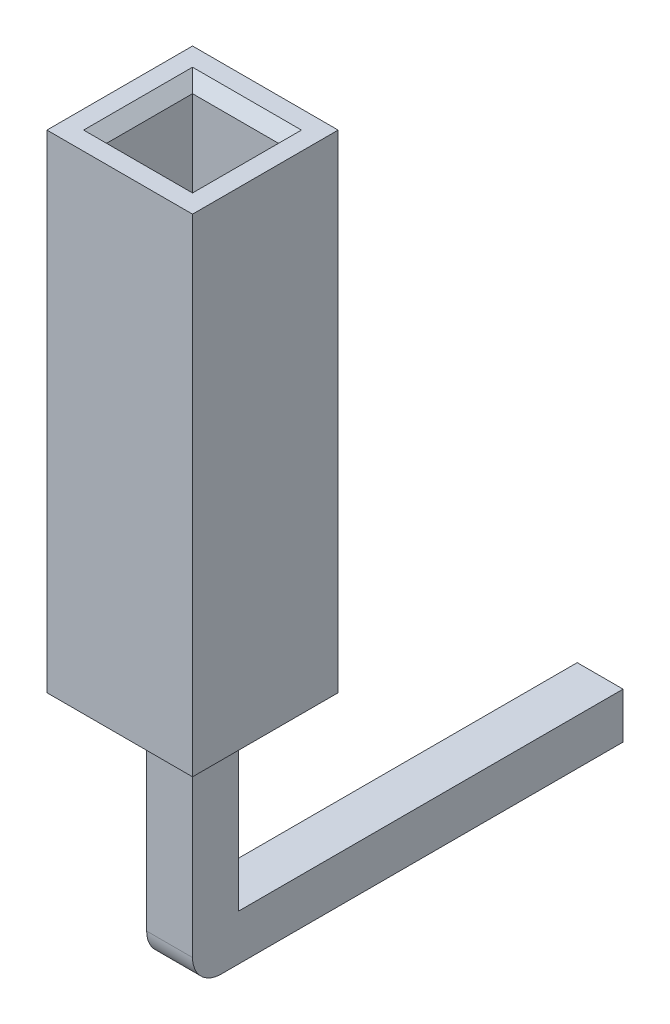
SolidWorks part; units mm, degrees
ref_plane "Спереди" through (0, 0, 0) normal (0, 0, 1) x (1, 0, 0)
ref_plane "Сверху" through (0, 0, 0) normal (0, 1, 0) x (1, 0, 0)
ref_plane "Справа" through (0, 0, 0) normal (1, 0, 0) x (0, 0, -1)
sketch "Эскиз1" plane through (0, 0, 0) normal (0, 1, 0) x (1, 0, 0)
  line L0 (1.27, 2.54) -> (1.27, 0) construction
  line L1 (0, 0) -> (2.54, 0)
  line L2 (0, 0) -> (0, 2.54)
  line L3 (0, 2.54) -> (2.54, 2.54)
  line L4 (2.54, 0) -> (2.54, 2.54)
  line L6 (0.52, 2.02) -> (2.02, 2.02)
  line L7 (0.52, 2.02) -> (0.52, 0.52)
  line L8 (0.52, 0.52) -> (2.02, 0.52)
  line L9 (2.02, 2.02) -> (2.02, 0.52)
  line L10 (0.52, 2.02) -> (2.02, 0.52) construction
  line L11 (0.52, 0.52) -> (2.02, 2.02) construction
  point P7 (1.27, 1.27)
  dimension "D1" = 2.54
  dimension "D2" = 1.5
extrude "Бобышка-Вытянуть1" add sketch "Эскиз1" along normal blind 8.5
sketch "Эскиз2" plane through (0, 0, 0) normal (0, -1, 0) x (1, 0, 0)
  line L0 (1.27, 0) -> (1.27, -2.54) construction
  line L1 (0, 0) -> (2.54, 0) construction
  line L2 (2.54, -2.54) -> (0, -2.54) construction
  line L4 (0.87, -0.87) -> (1.67, -0.87)
  line L5 (0.87, -0.87) -> (0.87, -1.67)
  line L6 (0.87, -1.67) -> (1.67, -1.67)
  line L7 (1.67, -0.87) -> (1.67, -1.67)
  line L8 (0.87, -0.87) -> (1.67, -1.67) construction
  line L9 (0.87, -1.67) -> (1.67, -0.87) construction
  point P6 (1.27, -1.27)
  point P7 (1.27, -1.27)
  dimension "D1" = 0.8
ref_plane "Плоскость1" through (1.27, 0, 0) normal (1, 0, 0) x (0, 0, -1)
sketch "Эскиз3" plane through (0.52, 0, 0) normal (1, 0, 0) x (0, 0, -1)
  line L0 (1.27, 0) -> (1.27, -1.16)
  line L1 (1.27, -1.16) -> (6.04, -1.16)
  line L2 (2.54, 8.5) -> (2.54, 0) construction
  line L3 (0, 8.5) -> (2.54, 8.5) construction
  dimension "D1" = 9.66
  dimension "D2" = 3.5
sweep "По траектории1" [suppressed] add profiles "Эскиз2" path "Эскиз3"
sketch "Эскиз4" plane through (1.27, 0, 0) normal (1, 0, 0) x (0, 0, -1)
  line L0 (1.27, 0) -> (1.27, -3.7)
  line L1 (1.27, -3.7) -> (8.58, -3.7)
  line L3 (0, 8.5) -> (2.54, 8.5) construction
  line L4 (2.54, 8.5) -> (2.54, 0) construction
  dimension "D1" = 12.2
  dimension "D2" = 6.04
sweep "По траектории2" add profiles "Эскиз2<2>" path "Эскиз4"
sketch "Эскиз2<2>" plane through (0, 0, 0) normal (0, -1, 0) x (1, 0, 0) same geometry as "Эскиз2"
chamfer "Фаска1" distance 0.2 angle 45 4 edges at (1.27, 8.5, -2.02) (2.02, 8.5, -1.27) (1.27, 8.5, -0.52) (0.52, 8.5, -1.27)
chamfer "Фаска2" [suppressed] distance 0.2 angle 45
chamfer "Фаска3" distance 0.2 angle 45 4 edges at (1.27, -3.3, -8.58) (0.87, -3.7, -8.58) (1.27, -4.1, -8.58) (1.67, -3.7, -8.58)
fillet "Скругление1" [suppressed] radius 0.5
fillet "Скругление2" radius 0.5 1 edges at (1.27, -4.1, -0.87)
